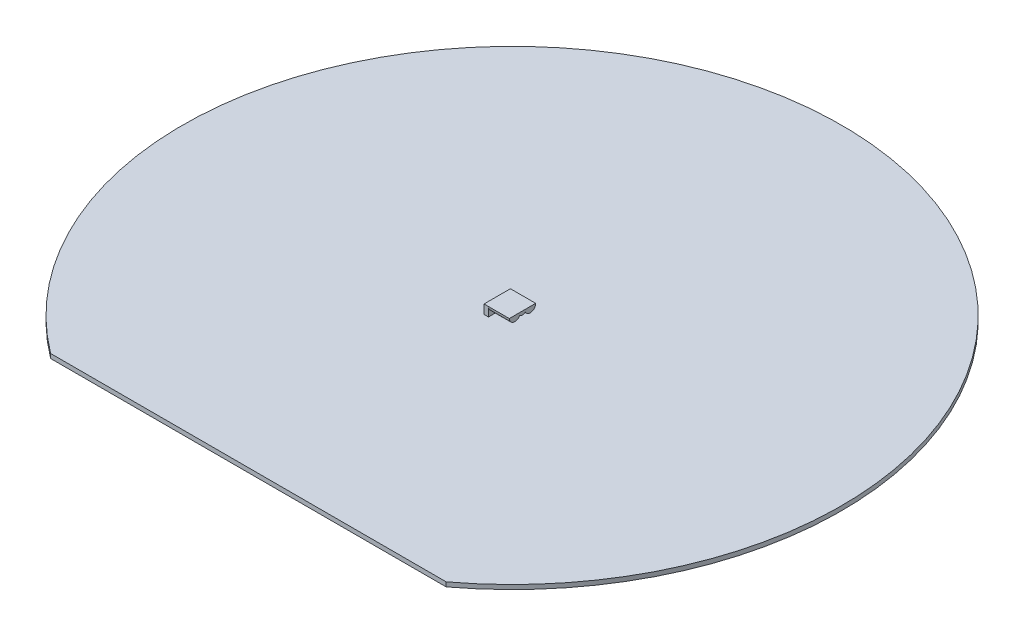
SolidWorks part; units mm, degrees
ref_plane "Plan de face" through (0, 0, 0) normal (0, 0, 1) x (1, 0, 0)
ref_plane "Plan de dessus" through (0, 0, 0) normal (0, 1, 0) x (1, 0, 0)
ref_plane "Plan de droite" through (0, 0, 0) normal (1, 0, 0) x (0, 0, -1)
sketch "Esquisse1" plane through (0, 0, 0) normal (0, 1, 0) x (1, 0, 0)
  circle A0 centre (0, 0) radius 150
  dimension "D1" = 300
extrude "Boss.-Extru.1" add sketch "Esquisse1" along normal blind 2
sketch "Esquisse2" plane through (0, 2, 0) normal (0, 1, 0) x (1, 0, 0)
  line L1 (-4.75, -6.75) -> (4.75, -6.75)
  line L2 (-4.75, -6.75) -> (-4.75, 6.75)
  line L3 (-4.75, 6.75) -> (4.75, 6.75)
  line L4 (4.75, -6.75) -> (4.75, 6.75)
  line L5 (-4.75, -6.75) -> (4.75, 6.75) construction
  line L6 (-4.75, 6.75) -> (4.75, -6.75) construction
  line L7 (-4.75, 6.75) -> (-6.75, 6.75)
  line L8 (-4.75, 6.75) -> (-4.75, -6.75)
  line L9 (-4.75, -6.75) -> (-6.75, -6.75)
  line L10 (-6.75, 6.75) -> (-6.75, -6.75)
  point P0 (0, 0)
  dimension "D1" = 9.5
  dimension "D2" = 13.5
  dimension "D3" = 2
extrude "Boss.-Extru.2" add sketch "Esquisse2" along normal blind 7 contours L7 L10 L9 L2 | L1 L4 L3 L2 region at (0, 2, 0) region at (-5.75, 2, 0)
sketch "Esquisse3" plane through (4.75, 0, 0) normal (1, 0, 0) x (0, 0, -1)
  line L1 (-6.75, 9) -> (-6.75, 2) construction
  line L2 (-6.75, 2) -> (6.75, 2) construction
  line L3 (-6, 6.15) -> (-6, 2)
  line L4 (6, 6.15) -> (6, 2)
  line L5 (150, 2) -> (-150, 2) construction
  line L6 (-6, 6.15) -> (6, 6.15)
  line L8 (-6.75, 9) -> (6.75, 9)
  line L9 (-6.75, 9) -> (-6.75, 2)
  line L10 (-6.75, 2) -> (6.75, 2)
  line L11 (6.75, 9) -> (6.75, 2)
  arc A0 (-1.65, 6.15) -> (1.65, 6.15) centre (0, 6.15) ccw
  arc A1 (-6, 6.15) -> (-1.2461, 5.0684) centre (-3.5, 6.15) ccw
  arc A2 (1.2461, 5.0684) -> (6, 6.15) centre (3.5, 6.15) ccw
  line M4 (-6.75, 2) -> (6.75, 2)
  line M5 (6.75, 2) -> (6.75, 9)
  line M6 (6.75, 9) -> (-6.75, 9)
  line M7 (-6.75, 9) -> (-6.75, 2)
  dimension "D4" = 5
  dimension "D5" = 5
  dimension "D6" = 3.3
  dimension "D7" = 3.25
  dimension "D1" = 3.5
  dimension "D2" = 3.5
  dimension "D3" = 4.15
extrude "Enlèv. mat.-Extru.2" cut sketch "Esquisse3" against normal blind 30 contours L3 L6 L4 M4 M5 M6 M7 region at (4.75, 7.0876, 0)
extrude "Enlèv. mat.-Extru.3" cut sketch "Esquisse3<3>" against normal blind 9.5 contours A2 A0 A1 L3 L4 M4 region at (4.75, 3.1737, 0)
sketch "Esquisse3<3>" plane through (4.75, 0, 0) normal (1, 0, 0) x (0, 0, -1) same geometry as "Esquisse3"
sketch "Esquisse4" plane through (0, 2, 0) normal (0, 1, 0) x (1, 0, 0)
  line L0 (-90, -120) -> (90, -120)
  circle A0 centre (0, 0) radius 150 construction
  arc A1 (-90, -120) -> (90, -120) centre (0, 0) ccw
  dimension "D1" = 120
extrude "Enlèv. mat.-Extru.4" cut sketch "Esquisse4" against normal through all
